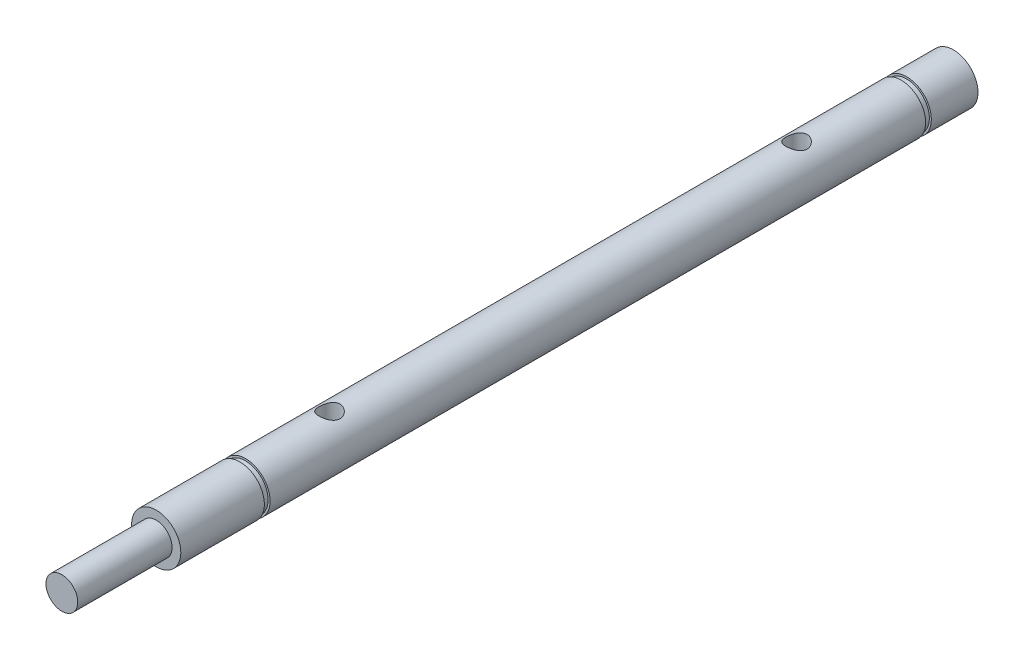
SolidWorks part; units mm, degrees
ref_plane "Front Plane" through (0, 0, 0) normal (0, 0, 1) x (1, 0, 0)
ref_plane "Top Plane" through (0, 0, 0) normal (0, 1, 0) x (1, 0, 0)
ref_plane "Right Plane" through (0, 0, 0) normal (1, 0, 0) x (0, 0, -1)
sketch "Sketch1" plane through (0, 0, 0) normal (0, 1, 0) x (1, 0, 0)
  line L0 (3.175, 99.7956) -> (-3.175, 99.7956) construction
  line L1 (4.915, -9.017) -> (-4.915, -9.017) construction
  line L2 (2.05, -1.5875) -> (2.05, -9.017) construction
  line L3 (4.915, -3.175) -> (-4.915, -3.175) construction
  line L6 (0, -1.5875) -> (0, 99.7956) construction
  line L7 (3.175, -1.5875) -> (3.175, 99.7956) construction
  line L8 (3.175, 99.7956) -> (0, 99.7956)
  line L9 (2.05, -9.017) -> (0, -9.017)
  line L10 (2.05, -3.175) -> (2.05, -9.017)
  line L11 (3.175, -3.175) -> (2.05, -3.175)
  line L14 (0, -9.017) -> (0, 99.7956)
  line L15 (3.175, -3.175) -> (3.175, 7.62)
  line L16 (3.175, 7.62) -> (2.921, 7.62) construction
  line L17 (2.921, 7.62) -> (2.921, 8.3566) construction
  line L18 (3.175, 8.3566) -> (2.921, 8.3566) construction
  line L19 (3.175, 93.0328) -> (2.921, 93.0328) construction
  line L20 (2.921, 93.7694) -> (2.921, 93.0328) construction
  line L21 (3.175, 93.7694) -> (2.921, 93.7694) construction
  line L22 (3.175, 7.62) -> (2.921, 7.62)
  line L23 (2.921, 7.62) -> (2.921, 8.3566)
  line L24 (3.175, 8.3566) -> (2.921, 8.3566)
  line L25 (3.175, 93.0328) -> (2.921, 93.0328)
  line L26 (2.921, 93.7694) -> (2.921, 93.0328)
  line L27 (3.175, 93.7694) -> (2.921, 93.7694)
  line L28 (3.175, 8.3566) -> (3.175, 93.0328)
  line L29 (3.175, 93.7694) -> (3.175, 99.7956)
  line L30 (4.7625, 14.4433) -> (-4.7625, 14.4433) construction
  line L31 (4.7625, 23.9683) -> (4.7625, 14.4433) construction
  line L32 (-4.7625, 23.9683) -> (-4.7625, 14.4433) construction
  line L33 (11.9063, 23.9683) -> (-11.9062, 23.9683) construction
  line L34 (4.7625, 74.7683) -> (4.7625, 84.2933) construction
  line L35 (-4.7625, 74.7683) -> (-4.7625, 84.2933) construction
  line L36 (4.7625, 84.2933) -> (-4.7625, 84.2933) construction
  line L37 (-4.7625, 74.7683) -> (4.7625, 74.7683) construction
  line L38 (4.7625, 14.4433) -> (-4.7625, 14.4433)
  line L39 (4.7625, 23.9683) -> (4.7625, 14.4433)
  line L40 (-4.7625, 23.9683) -> (-4.7625, 14.4433)
  line L41 (4.7625, 23.9683) -> (-4.7625, 23.9683)
  line L42 (4.7625, 74.7683) -> (4.7625, 84.2933)
  line L43 (-4.7625, 74.7683) -> (-4.7625, 84.2933)
  line L44 (4.7625, 84.2933) -> (-4.7625, 84.2933)
  line L45 (-4.7625, 74.7683) -> (4.7625, 74.7683)
  line L46 (0, 84.2933) -> (0, 74.7683) construction
  line L47 (0, 23.9683) -> (0, 14.4433) construction
  point P38 (0, 79.5308)
  point P39 (0, 19.2058)
revolve "Revolve1" add sketch "Sketch1" angle 360 about L14 region at (1.5819, 0, -92.0392) region at (1.5875, 0, -79.5308) region at (1.5875, 0, -49.3683) region at (1.5875, 0, -19.2058) region at (1.484, 0, -3.5534)
ref_plane "Plane1" through (0, -3.175, 0) normal (0, -1, 0) x (-1, 0, 0)
hole_wizard "#6-32 Tapped Hole1" positions "Sketch2" profile "Sketch3" tap size "#6-32" standard "ANSI Inch"
sketch "Sketch2" plane through (0, -3.175, 0) normal (0, -1, 0) x (-1, 0, 0)
  point P0 (0, 79.5308)
  point P2 (0, 19.2058)
sketch "Sketch3" plane through (0, -3.175, -79.5308) normal (1, 0, 0) x (0, 0, -1)
  line L0 (0, 0) -> (0, 10.2107)
  line L1 (0, 10.2107) -> (1.3525, 9.398)
  line L2 (1.3525, 9.398) -> (1.3525, 0)
  line L5 (1.3525, 0) -> (0, 0)
  line L10 (0, 10.2107) -> (-1.3525, 9.398) construction
  line L11 (0, -6.35) -> (0, 107.95) construction
  dimension "Tap Drill Dia." = 2.7051
  dimension "Tap Drill Depth" = 9.398
  dimension "Drill Angle" = 118
cosmetic thread "Hole Thread2" parameters "D1"=6.35, "D2"=3.5052
cosmetic thread "Hole Thread3" parameters "D1"=6.35, "D2"=3.5052
sketch "Sketch4" plane through (0, 0, 9.017) normal (0, 0, 1) x (1, 0, 0)
  circle A0 centre (0, 0) radius 2.05 construction
  circle A1 centre (0, 0) radius 2.05
extrude "Boss-Extrude1" add sketch "Sketch4" along normal blind 6.35
